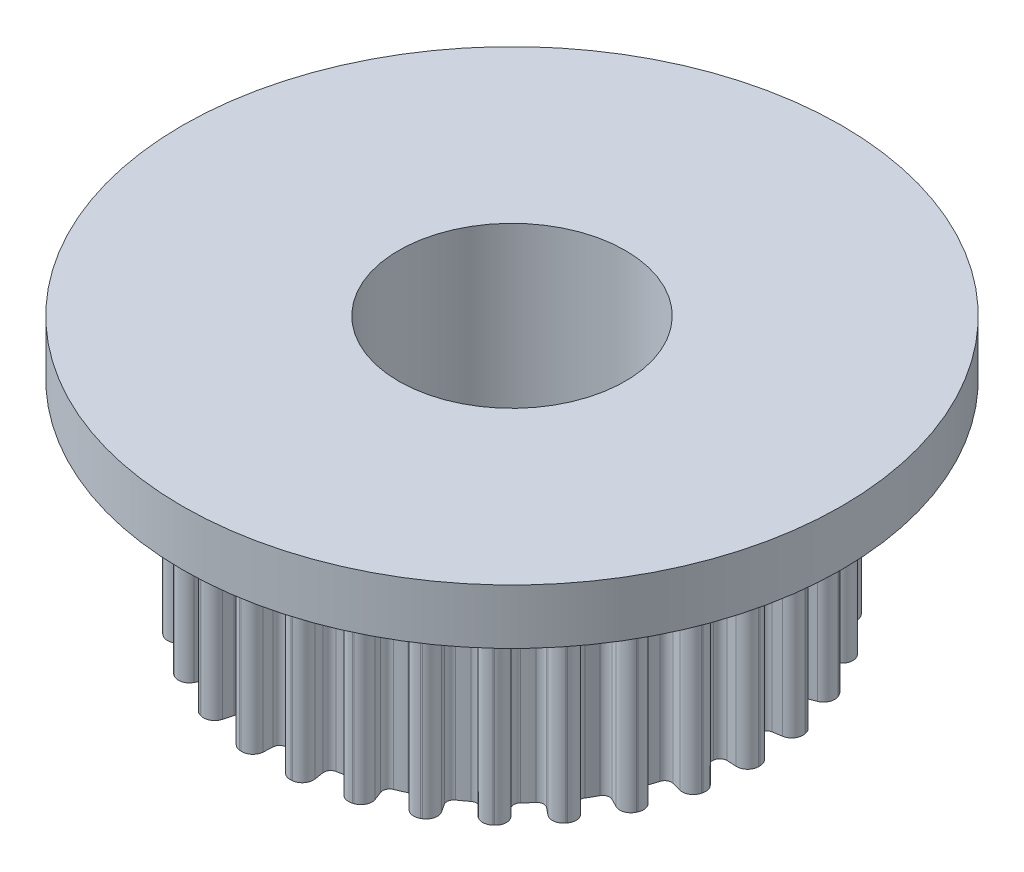
SolidWorks part; units mm, degrees
material "PET"
ref_plane "Front Plane" through (0, 0, 0) normal (0, 0, 1) x (1, 0, 0)
ref_plane "Top Plane" through (0, 0, 0) normal (0, 1, 0) x (1, 0, 0)
ref_plane "Right Plane" through (0, 0, 0) normal (1, 0, 0) x (0, 0, -1)
sketch "Sketch1" plane through (0, 0, 0) normal (0, 1, 0) x (1, 0, 0)
  circle A0 centre (0, 0) radius 4.125
  circle A1 centre (0, 0) radius 9
  dimension "D1" = 8.25
  dimension "D2" = 18
extrude "Boss-Extrude1" add sketch "Sketch1" along normal blind 7.7
sketch "Sketch2" plane through (0, 7.7, 0) normal (0, 1, 0) x (1, 0, 0)
  line L0 (0, 0) -> (0, -9) construction
  line L1 (0, 0) -> (0.5, -8.9861)
  line L6 (0, 0) -> (-0.5, -8.9861)
  circle A0 centre (0, 0) radius 9 construction
  circle A1 centre (0, 0) radius 8
  circle A2 centre (0, 0) radius 9
  point P8 (0.4444, -7.9876)
  circle M8 centre (0, 0) radius 9
  dimension "D1" = 1
  dimension "D2" = 1
extrude "Cut-Extrude1" cut sketch "Sketch2" against normal through all contours A1 L0 A2 L1 | L0 A1 L6 M8 region at (0.2364, 7.7, 8.5054) region at (-0.2364, 7.7, 8.5054)
fillet "Fillet1" radius 0.25 2 edges at (0.4444, 3.85, 7.9876) (-0.4444, 3.85, 7.9876)
fillet "Fillet2" radius 0.4 2 edges at (0.5, 3.85, 8.9861) (-0.5, 3.85, 8.9861)
ref_axis "Axis1" through (0, 7.7, 0) along (0, -1, 0)
pattern_circular "CirPattern1" count 30 over 360 about axis through (0, 7.7, 0) along (0, -1, 0) of "Cut-Extrude1", "Fillet1", "Fillet2"
sketch "Sketch3" plane through (0, 7.7, 0) normal (0, 1, 0) x (1, 0, 0)
  circle A0 centre (0, 0) radius 12
  circle A1 centre (0, 0) radius 4.125
  circle A2 centre (0, 0) radius 4.125 construction
  dimension "D1" = 24
extrude "Boss-Extrude2" add sketch "Sketch3" along normal blind 2
